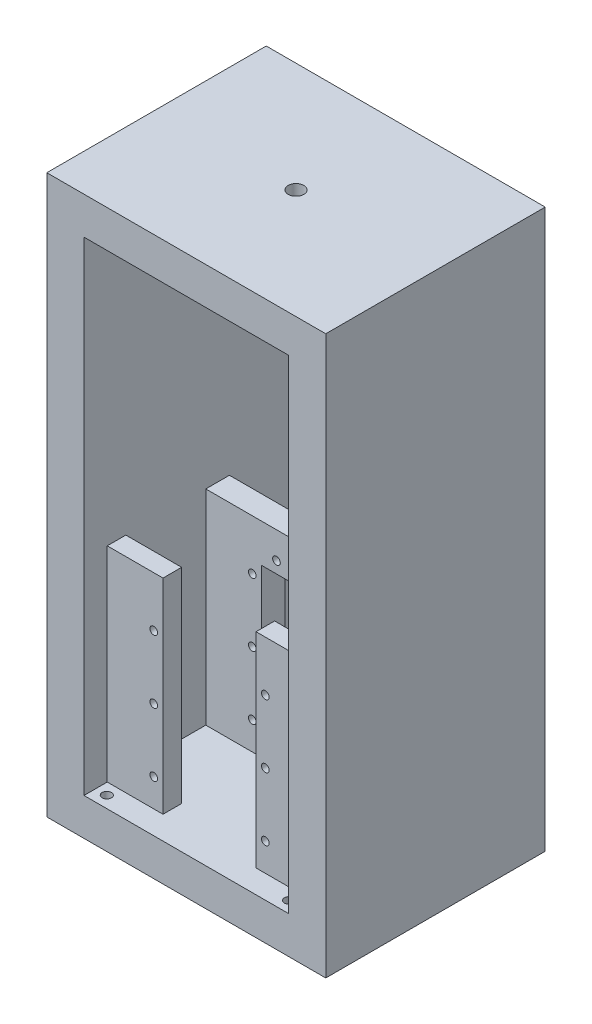
SolidWorks part; units mm, degrees
material "PET"
ref_plane "Front Plane" through (0, 0, 0) normal (0, 0, 1) x (1, 0, 0)
ref_plane "Top Plane" through (0, 0, 0) normal (0, 1, 0) x (1, 0, 0)
ref_plane "Right Plane" through (0, 0, 0) normal (1, 0, 0) x (0, 0, -1)
sketch "Sketch1" plane through (0, 0, 0) normal (0, 0, 1) x (1, 0, 0)
  line L1 (0, 0) -> (75, 0)
  line L2 (0, 0) -> (0, 150)
  line L3 (0, 150) -> (75, 150)
  line L4 (75, 0) -> (75, 150)
  line L5 (10, 10) -> (65, 10)
  line L6 (10, 10) -> (10, 140)
  line L7 (10, 140) -> (65, 140)
  line L8 (65, 10) -> (65, 140)
  dimension "D1" = 75
  dimension "D2" = 150
  dimension "D3" = 10
  dimension "D4" = 10
  dimension "D5" = 10
  dimension "D6" = 10
extrude "Boss-Extrude1" add sketch "Sketch1" against normal blind 59
ref_plane "Plane1" through (0, 0, -37.5) normal (0, 0, 1) x (1, 0, 0)
hole_wizard "Tap Drill for M5x0.8 Tap2" positions "Sketch8" profile "Sketch9" hole size "M5x0.8" standard "ANSI Metric" end condition through all
sketch "Sketch8" plane through (0, 10, 0) normal (0, 1, 0) x (1, 0, 0)
  line L0 (37.5, 59) -> (37.5, 0) construction
  line L1 (10, 59) -> (65, 59) construction
  line L2 (10, 0) -> (65, 0) construction
  point P0 (37.5, 29.5)
sketch "Sketch9" plane through (37.5, 10, -29.5) normal (1, 0, 0) x (0, 0, 1)
  line L0 (0, 0) -> (0, 10)
  line L1 (0, 10) -> (2.1, 10)
  line L2 (2.1, 10) -> (2.1, 0)
  line L5 (2.1, 0) -> (0, 0)
  line L11 (0, -6.35) -> (0, 107.95) construction
  dimension "Thru Hole Dia." = 4.2
  dimension "Thru Hole Depth" = 10
hole_wizard "Tap Drill for M5x0.8 Tap3" positions "Sketch11" profile "Sketch12" hole size "M5x0.8" standard "ANSI Metric"
sketch "Sketch11" plane through (0, 150, 0) normal (0, 1, 0) x (1, 0, 0)
  line L0 (0, 29.5) -> (75, 29.5) construction
  line L1 (0, 59) -> (0, 0) construction
  line L2 (75, 59) -> (75, 0) construction
  point P0 (37.5, 29.5)
sketch "Sketch12" plane through (37.5, 150, -29.5) normal (1, 0, 0) x (0, 0, 1)
  line L0 (0, 0) -> (0, 11.2618)
  line L1 (0, 11.2618) -> (2.1, 10)
  line L2 (2.1, 10) -> (2.1, 0)
  line L5 (2.1, 0) -> (0, 0)
  line L10 (0, 11.2618) -> (-2.1, 10) construction
  line L11 (0, -6.35) -> (0, 107.95) construction
  dimension "Hole Dia." = 4.2
  dimension "Hole Depth" = 10
  dimension "Drill Angle" = 118
sketch "Sketch13" plane through (0, 10, 0) normal (0, 1, 0) x (1, 0, 0)
  line L0 (65, 59) -> (65, 0) construction
  line L1 (65, 32.75) -> (50, 32.75)
  line L2 (65, 32.75) -> (65, 39.1)
  line L3 (65, 39.1) -> (50, 39.1)
  line L4 (50, 32.75) -> (50, 39.1)
  line L5 (37.5, 59) -> (37.5, 0) construction
  line L6 (10, 59) -> (65, 59) construction
  line L7 (10, 0) -> (65, 0) construction
  line L8 (10, 39.1) -> (25, 39.1)
  line L9 (25, 32.75) -> (25, 39.1)
  line L10 (10, 32.75) -> (25, 32.75)
  line L11 (10, 32.75) -> (10, 39.1)
  line L12 (10, 11.25) -> (25, 11.25)
  line L13 (65, 6.25) -> (50, 6.25)
  line L14 (65, 6.25) -> (65, 11.25)
  line L15 (65, 11.25) -> (50, 11.25)
  line L16 (50, 6.25) -> (50, 11.25)
  line L17 (25, 6.25) -> (25, 11.25)
  line L18 (10, 6.25) -> (25, 6.25)
  line L19 (10, 6.25) -> (10, 11.25)
  dimension "D1" = 26.25
  dimension "D2" = 12.5
  dimension "D3" = 6.35
  dimension "D4" = 6.25
  dimension "D5" = 5
  dimension "D6" = 15
extrude "Boss-Extrude2" add sketch "Sketch13" along normal blind 55
sketch "Sketch14" plane through (50, 0, 0) normal (-1, 0, 0) x (0, 0, 1)
  line L0 (-32.75, 65) -> (-32.75, 10) construction
  line L1 (-39.1, 65) -> (-32.75, 65)
  line L2 (-39.1, 65) -> (-39.1, 54.7)
  line L3 (-39.1, 54.7) -> (-32.75, 54.7)
  line L4 (-32.75, 65) -> (-32.75, 54.7)
  dimension "D1" = 10.3
extrude "Boss-Extrude3" add sketch "Sketch14" along normal up to surface (25 mm away) contours L1 L4 L3 L2 up to face at (25, 37.5, -35.925)
sketch "Sketch17" plane through (0, 0, -39.1) normal (0, 0, -1) x (-1, 0, 0)
  line L0 (-37.5, 65) -> (-37.5, 10) construction
  line L1 (-65, 65) -> (-10, 65) construction
  line L2 (-10, 10) -> (-65, 10) construction
  line L3 (-22.5, 65) -> (-22.5, 10) construction
  line L5 (-25, 10) -> (-10, 10) construction
  line L6 (-29, 65) -> (-29, 10) construction
  line L8 (-65, 17.5) -> (-10, 17.5) construction
  line L9 (-65, 10) -> (-65, 140) construction
  line L10 (-10, 65) -> (-10, 10) construction
  line L11 (-65, 34.5) -> (-10, 34.5) construction
  line L12 (-65, 51.5) -> (-10, 51.5) construction
  line L13 (-65, 57.8) -> (-10, 57.8) construction
  line L14 (-52.5, 65) -> (-52.5, 10) construction
  line L15 (-46, 65) -> (-46, 10) construction
  dimension "D1" = 15
  dimension "D2" = 6.5
  dimension "D3" = 7.5
  dimension "D4" = 17
  dimension "D5" = 17
  dimension "D6" = 6.3
hole_wizard "Tap Drill for M2.5x0.45 Tap1" positions "Sketch18" profile "Sketch19" hole size "M2.5x0.45" standard "ANSI Metric" end condition through all
sketch "Sketch18" plane through (0, 0, -39.1) normal (0, 0, -1) x (-1, 0, 0)
  line L0 (-65, 57.8) -> (-10, 57.8) construction
  line L1 (-46, 65) -> (-46, 10) construction
  line L2 (-29, 65) -> (-29, 10) construction
  line L3 (-22.5, 65) -> (-22.5, 10) construction
  line L4 (-65, 51.5) -> (-10, 51.5) construction
  line L5 (-52.5, 65) -> (-52.5, 10) construction
  line L6 (-65, 34.5) -> (-10, 34.5) construction
  line L7 (-65, 17.5) -> (-10, 17.5) construction
  point P0 (-46, 57.8)
  point P2 (-52.5, 51.5)
  point P4 (-52.5, 34.5)
  point P6 (-52.5, 17.5)
  point P8 (-22.5, 17.5)
  point P10 (-22.5, 34.5)
  point P12 (-22.5, 51.5)
  point P14 (-29, 57.8)
sketch "Sketch19" plane through (46, 57.8, -39.1) normal (1, 0, 0) x (0, 1, 0)
  line L0 (0, 0) -> (0, 39.1)
  line L1 (0, 39.1) -> (1.025, 39.1)
  line L2 (1.025, 39.1) -> (1.025, 0)
  line L5 (1.025, 0) -> (0, 0)
  line L11 (0, -6.35) -> (0, 107.95) construction
  dimension "Thru Hole Dia." = 2.05
  dimension "Thru Hole Depth" = 39.1
hole_wizard "Tap Drill for M3x0.5 Tap1" positions "Sketch20" profile "Sketch21" hole size "M3x0.5" standard "ANSI Metric" end condition through all
sketch "Sketch20" plane through (0, 10, 0) normal (0, 1, 0) x (1, 0, 0)
  line L0 (10, 3.125) -> (65, 3.125) construction
  line L1 (10, 6.25) -> (10, 0) construction
  line L2 (65, 6.25) -> (65, 0) construction
  line L4 (13, 6.25) -> (13, 0) construction
  line L5 (10, 6.25) -> (25, 6.25) construction
  line L6 (10, 0) -> (65, 0) construction
  line L8 (62, 6.25) -> (62, 0) construction
  line L9 (50, 6.25) -> (65, 6.25) construction
  line L11 (65, 53) -> (10, 53)
  line L12 (65, 59) -> (65, 39.1) construction
  line L13 (10, 59) -> (10, 39.1) construction
  line L15 (10, 59) -> (65, 59) construction
  line L16 (60, 53) -> (60, 59) construction
  line L18 (15, 53) -> (15, 59) construction
  point P0 (13, 3.125)
  point P2 (62, 3.125)
  point P37 (60, 53)
  point P39 (15, 53)
  dimension "D1" = 3
  dimension "D2" = 3
  dimension "D3" = 6
  dimension "D4" = 5
  dimension "D5" = 5
sketch "Sketch21" plane through (13, 10, -3.125) normal (1, 0, 0) x (0, 0, 1)
  line L0 (0, 0) -> (0, 10)
  line L1 (0, 10) -> (1.25, 10)
  line L2 (1.25, 10) -> (1.25, 0)
  line L5 (1.25, 0) -> (0, 0)
  line L11 (0, -6.35) -> (0, 107.95) construction
  dimension "Thru Hole Dia." = 2.5
  dimension "Thru Hole Depth" = 10
